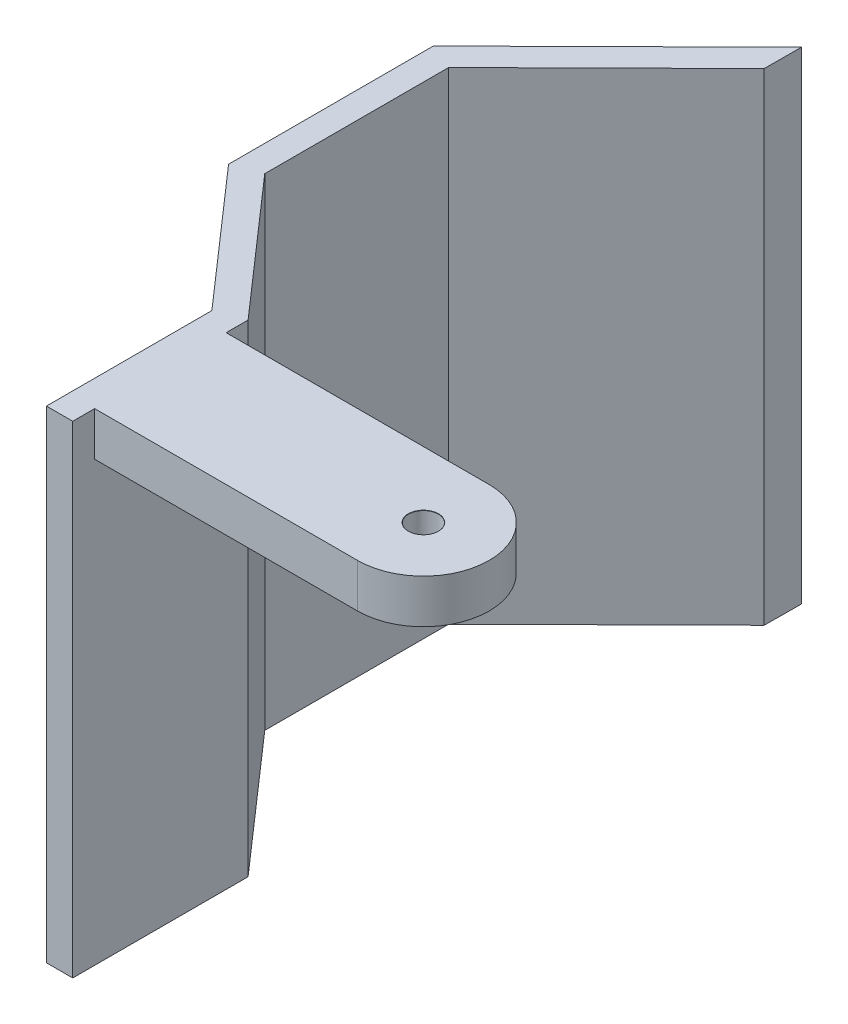
SolidWorks part; units mm, degrees
ref_plane "Front Plane" through (0, 0, 0) normal (0, 0, 1) x (1, 0, 0)
ref_plane "Top Plane" through (0, 0, 0) normal (0, 1, 0) x (1, 0, 0)
ref_plane "Right Plane" through (0, 0, 0) normal (1, 0, 0) x (0, 0, -1)
sketch "Sketch1" plane through (0, 0, 0) normal (0, 1, 0) x (1, 0, 0)
  line L0 (0, 0) -> (0, 18.8714)
  line L1 (0, 18.8714) -> (-13.5055, 34.2807)
  line L2 (-13.5055, 34.2807) -> (-13.5055, 57.6371)
  line L3 (-13.5055, 57.6371) -> (7.6165, 78.5217)
  line L9 (3, 0) -> (0, 0)
  line L10 (9.3102, 0) -> (0, 0) construction
  line L12 (3, 20) -> (-10.5055, 35.4093)
  line L13 (-10.5055, 35.4093) -> (-10.5055, 56.3845)
  line L14 (-10.5055, 56.3845) -> (7.5925, 74.2792)
  line L15 (7.5925, 74.2792) -> (7.6165, 78.5217)
  line L16 (9.3102, 3) -> (3, 3) construction
  line L18 (7.5925, 74.2792) -> (12.0785, 69.7422) construction
  line L19 (7.6165, 78.5217) -> (14.2117, 71.8516) construction
  line L20 (3, 0) -> (3, 20)
  line L21 (3, 3) -> (3, 20) construction
  line L22 (3, 2.5) -> (33, 2.5)
  line L23 (3, 17.5) -> (33, 17.5)
  arc A0 (33, 2.5) -> (33, 17.5) centre (33, 10) ccw
  point P22 (3, 10)
  dimension "D2" = 15
  dimension "D1" = 3
  dimension "D3" = 30
  dimension "D4" = 20
extrude "Boss-Extrude1" add sketch "Sketch1" along normal blind 55 contours L9 L20 L12 L13 L14 L15 L3 L2 L1 L0 region at (0.8131, 0, -9.4357)
extrude "Boss-Extrude2" add sketch "Sketch1<3>" against normal blind 5 from surface contours L22 A0 L23 L20 region at (20.9843, 0, -10) starting at face at (-2.6813, 55, -37.5384)
sketch "Sketch1<3>" plane through (0, 0, 0) normal (0, 1, 0) x (1, 0, 0) same geometry as "Sketch1"
ref_axis "GearAxis" through (33, 50, -10) along (0, 1, 0)
hole_wizard "M3 Clearance Hole1" positions "Sketch2" profile "Sketch3" hole size "M3" standard "ANSI Metric" end condition through all
sketch "Sketch2" plane through (0, 55, 0) normal (0, 1, 0) x (1, 0, 0)
  point P0 (33, 10)
sketch "Sketch3" plane through (33, 55, -10) normal (1, 0, 0) x (0, 0, 1)
  line L0 (0, 0) -> (0, 55)
  line L1 (0, 55) -> (1.7, 55)
  line L2 (1.7, 55) -> (1.7, 0.025)
  line L3 (1.7, 0.025) -> (1.725, 0)
  line L5 (1.725, 0) -> (0, 0)
  line L6 (-1.7, 0.025) -> (-1.725, 0) construction
  line L11 (0, -6.35) -> (0, 107.95) construction
  dimension "Thru Hole Dia." = 3.4
  dimension "Thru Hole Depth" = 55
  dimension "Near C'Sink Dia." = 3.45
  dimension "Near C'Sink Angle" = 90
